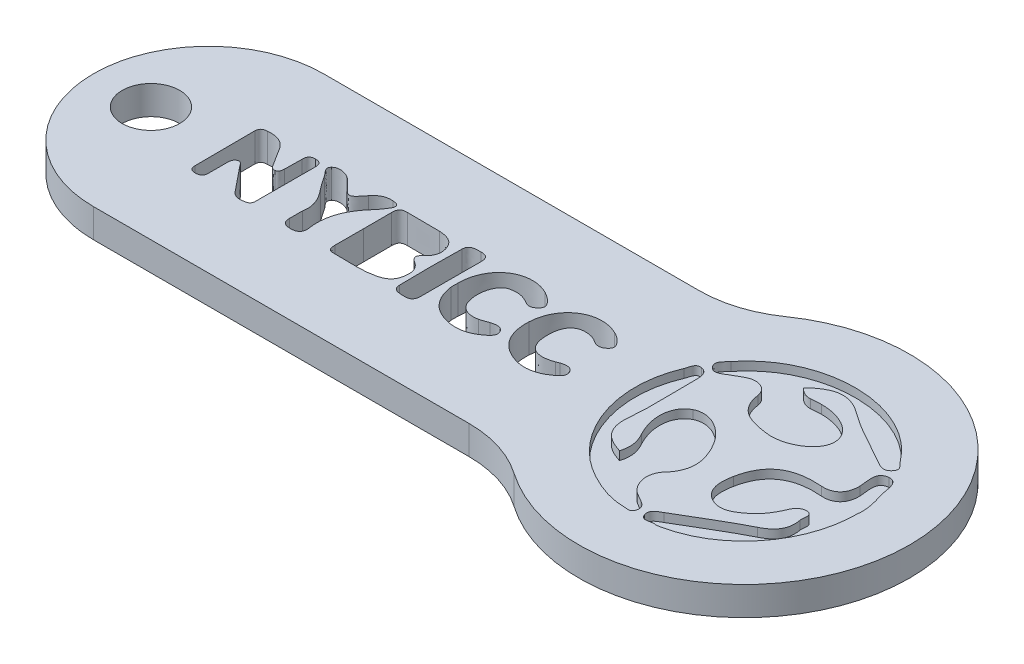
SolidWorks part; units mm, degrees
ref_plane "Plan de face" through (0, 0, 0) normal (0, 0, 1) x (1, 0, 0)
ref_plane "Plan de dessus" through (0, 0, 0) normal (0, 1, 0) x (1, 0, 0)
ref_plane "Plan de droite" through (0, 0, 0) normal (1, 0, 0) x (0, 0, -1)
sketch "Esquisse1" plane through (0, 0, 0) normal (0, 1, 0) x (1, 0, 0)
  line L0 (-14.5, 0) -> (0, 0) construction
  line L1 (-18.5, 8) -> (18.5, 8)
  line L2 (-18.5, 8) -> (-18.5, -8)
  line L3 (-18.5, -8) -> (18.5, -8)
  line L5 (-18.5, 8) -> (18.5, -8) construction
  line L6 (-18.5, -8) -> (18.5, 8) construction
  arc A0 (18.5, -8) -> (18.5, 8) centre (26.7614, 0) ccw
  circle A1 centre (-14.5, 0) radius 2
  point P0 (0, 0)
  dimension "D3" = 23
  dimension "D5" = 4
  dimension "D1" = 37
  dimension "D2" = 16
  dimension "D4" = 4
extrude "Boss.-Extru.1" add sketch "Esquisse1" along normal blind 2
sketch "Esquisse2" plane through (0, 2, 0) normal (0, 1, 0) x (1, 0, 0)
  line L0 (20.6551, -5.913) -> (-11.0872, -5.913)
  line L1 (-11.0872, -5.913) -> (-11.0872, 5.913)
  line L2 (-11.0872, 5.913) -> (20.6551, 5.913)
  line L3 (20.6551, 5.913) -> (20.5787, 5.7726)
  line L7 (18.5, 8) -> (-18.5, 8)
  line L8 (-18.5, 8) -> (-18.5, -8)
  line L9 (-18.5, -8) -> (18.5, -8)
  line L10 (18.5, 8) -> (-18.5, 8)
  line L11 (-18.5, 8) -> (-18.5, -8)
  line L12 (-18.5, -8) -> (18.5, -8)
  arc A2 (20.6551, -5.913) -> (20.6551, 5.913) centre (26.7614, 0) ccw
  arc A3 (20.6551, -5.913) -> (20.6551, 5.913) centre (26.7614, 0) ccw
  arc A4 (18.5, -8) -> (18.5, 8) centre (26.7614, 0) ccw
  arc A5 (18.5, -8) -> (18.5, 8) centre (26.7614, 0) ccw
  spline S0 degree 3 poles (0.225, -1.9246) (0.2286, -1.2609) (0.2275, -0.5975) (0.2283, 0.0661) knots 10 10 10 10 11 11 11 11
  spline S1 degree 3 poles (0.6284, -2.4527) (0.2813, -2.4644) (0.2234, -2.2089) (0.225, -1.9246) knots 9 9 9 9 10 10 10 10
  spline S2 degree 3 poles (3.5067, -2.3468) (2.5542, -2.5708) (1.5879, -2.4206) (0.6284, -2.4527) knots 8 8 8 8 9 9 9 9
  spline S3 degree 3 poles (4.4683, -1.5249) (4.3523, -2.028) (3.9703, -2.238) (3.5067, -2.3468) knots 7 7 7 7 8 8 8 8
  spline S4 degree 3 poles (4.0132, -0.175) (4.5319, -0.4973) (4.5922, -0.9877) (4.4683, -1.5249) knots 6 6 6 6 7 7 7 7
  spline S5 degree 3 poles (3.9341, 0.5259) (3.6149, 0.2483) (3.6818, 0.0309) (4.0132, -0.175) knots 5 5 5 5 6 6 6 6
  spline S6 degree 3 poles (4.2394, 1.8576) (4.4545, 1.3474) (4.3569, 0.8935) (3.9341, 0.5259) knots 4 4 4 4 5 5 5 5
  spline S7 degree 3 poles (3.0323, 2.5476) (3.5345, 2.5261) (4.0161, 2.3873) (4.2394, 1.8576) knots 3 3 3 3 4 4 4 4
  spline S8 degree 3 poles (0.7853, 2.5646) (1.5338, 2.5425) (2.2844, 2.5795) (3.0323, 2.5476) knots 2 2 2 2 3 3 3 3
  spline S9 degree 3 poles (0.2259, 1.9923) (0.215, 2.3984) (0.3606, 2.5772) (0.7853, 2.5646) knots 1 1 1 1 2 2 2 2
  spline S10 degree 3 poles (0.2283, 0.0661) (0.2291, 0.7082) (0.243, 1.3507) (0.2259, 1.9923) knots 0 0 0 0 1 1 1 1
  spline S11 degree 3 poles (-5.1722, 2.1197) (-5.1775, 1.4133) (-5.1754, 0.7068) (-5.176, 0.0003) knots 18 18 18 18 19 19 19 19
  spline S12 degree 3 poles (-5.6399, 2.5867) (-5.3196, 2.5835) (-5.1698, 2.4412) (-5.1722, 2.1197) knots 17 17 17 17 18 18 18 18
  spline S13 degree 3 poles (-6.0939, 2.115) (-6.0989, 2.4345) (-5.9709, 2.5902) (-5.6399, 2.5867) knots 16 16 16 16 17 17 17 17
  spline S14 degree 3 poles (-6.114, 0.896) (-6.0883, 1.3013) (-6.0877, 1.7087) (-6.0939, 2.115) knots 15 15 15 15 16 16 16 16
  spline S15 degree 3 poles (-6.3567, 0.4874) (-6.1454, 0.5282) (-6.1242, 0.7367) (-6.114, 0.896) knots 14 14 14 14 15 15 15 15
  spline S16 degree 3 poles (-6.7563, 0.7516) (-6.663, 0.6061) (-6.5561, 0.4488) (-6.3567, 0.4874) knots 13 13 13 13 14 14 14 14
  spline S17 degree 3 poles (-7.4724, 1.8877) (-7.2442, 1.5028) (-6.998, 1.1285) (-6.7563, 0.7516) knots 12 12 12 12 13 13 13 13
  spline S18 degree 3 poles (-8.9993, 2.5914) (-8.3468, 2.6534) (-7.8223, 2.4779) (-7.4724, 1.8877) knots 11 11 11 11 12 12 12 12
  spline S19 degree 3 poles (-9.4508, 2.1725) (-9.4369, 2.4583) (-9.2899, 2.5782) (-8.9993, 2.5914) knots 10 10 10 10 11 11 11 11
  spline S20 degree 3 poles (-9.4291, -2.0014) (-9.4372, -0.6101) (-9.4441, 0.7812) (-9.4508, 2.1725) knots 9 9 9 9 10 10 10 10
  spline S21 degree 3 poles (-9.0021, -2.437) (-9.2963, -2.4301) (-9.4357, -2.2901) (-9.4291, -2.0014) knots 8 8 8 8 9 9 9 9
  spline S22 degree 3 poles (-8.5069, -2.0014) (-8.512, -2.3343) (-8.6938, -2.4441) (-9.0021, -2.437) knots 7 7 7 7 8 8 8 8
  spline S23 degree 3 poles (-8.5036, -0.717) (-8.5043, -1.1452) (-8.5101, -1.5733) (-8.5069, -2.0014) knots 6 6 6 6 7 7 7 7
  spline S24 degree 3 poles (-8.2858, -0.219) (-8.4821, -0.3042) (-8.5032, -0.5178) (-8.5036, -0.717) knots 5 5 5 5 6 6 6 6
  spline S25 degree 3 poles (-7.8369, -0.4857) (-7.953, -0.3438) (-8.0529, -0.1181) (-8.2858, -0.219) knots 4 4 4 4 5 5 5 5
  spline S26 degree 3 poles (-6.4635, -2.1807) (-6.9172, -1.6123) (-7.376, -1.0481) (-7.8369, -0.4857) knots 3 3 3 3 4 4 4 4
  spline S27 degree 3 poles (-5.4688, -2.4272) (-5.8242, -2.5108) (-6.1923, -2.5206) (-6.4635, -2.1807) knots 2 2 2 2 3 3 3 3
  spline S28 degree 3 poles (-5.1794, -1.7337) (-5.182, -2.003) (-5.1008, -2.3406) (-5.4688, -2.4272) knots 1 1 1 1 2 2 2 2
  spline S29 degree 3 poles (-5.176, 0.0003) (-5.1766, -0.5777) (-5.174, -1.1557) (-5.1794, -1.7337) knots 0 0 0 0 1 1 1 1
  spline S30 degree 3 poles (14.6022, 1.5071) (13.5928, 1.7408) (13.0414, 1.2329) (13.0294, 0.0773) knots 11 11 11 11 12 12 12 12
  spline S31 degree 3 poles (15.1149, 1.2613) (14.9529, 1.3592) (14.7827, 1.4653) (14.6022, 1.5071) knots 10 10 10 10 11 11 11 11
  spline S32 degree 3 poles (15.9779, 1.4079) (15.76, 1.1539) (15.4505, 1.0583) (15.1149, 1.2613) knots 9 9 9 9 10 10 10 10
  spline S33 degree 3 poles (15.7902, 2.127) (15.9828, 1.9215) (16.214, 1.683) (15.9779, 1.4079) knots 8 8 8 8 9 9 9 9
  spline S34 degree 3 poles (15.1624, 2.5592) (15.3993, 2.452) (15.6134, 2.3158) (15.7902, 2.127) knots 7 7 7 7 8 8 8 8
  spline S35 degree 3 poles (11.588, 0.203) (11.6856, 2.2051) (13.4456, 3.3361) (15.1624, 2.5592) knots 6 6 6 6 7 7 7 7
  spline S36 degree 3 poles (12.9311, -2.3704) (11.8989, -1.8387) (11.5353, -0.8789) (11.588, 0.203) knots 5 5 5 5 6 6 6 6
  spline S37 degree 3 poles (15.6465, -2.1778) (14.7863, -2.8026) (13.8563, -2.8469) (12.9311, -2.3704) knots 4 4 4 4 5 5 5 5
  spline S38 degree 3 poles (16.0103, -1.3913) (16.2116, -1.7555) (15.9033, -1.9912) (15.6465, -2.1778) knots 3 3 3 3 4 4 4 4
  spline S39 degree 3 poles (15.1543, -1.1929) (15.4802, -1.0869) (15.8296, -1.0644) (16.0103, -1.3913) knots 2 2 2 2 3 3 3 3
  spline S40 degree 3 poles (14.9188, -1.2919) (14.9993, -1.2645) (15.0736, -1.2191) (15.1543, -1.1929) knots 1 1 1 1 2 2 2 2
  spline S41 degree 3 poles (13.0294, 0.0773) (13.0157, -1.2291) (13.6832, -1.7132) (14.9188, -1.2919) knots 0 0 0 0 1 1 1 1
  spline S42 degree 3 poles (6.7883, -0.4372) (6.7642, -0.2695) (6.7853, -0.0953) (6.7855, 0.0759) knots 13 13 13 13 14 14 14 14
  spline S43 degree 3 poles (8.2655, -2.4564) (7.3765, -2.0939) (6.9224, -1.3698) (6.7883, -0.4372) knots 12 12 12 12 13 13 13 13
  spline S44 degree 3 poles (10.8143, -2.1643) (10.0263, -2.763) (9.1527, -2.8182) (8.2655, -2.4564) knots 11 11 11 11 12 12 12 12
  spline S45 degree 3 poles (11.1531, -1.3675) (11.3657, -1.7257) (11.0713, -1.969) (10.8143, -2.1643) knots 10 10 10 10 11 11 11 11
  spline S46 degree 3 poles (10.2831, -1.1939) (10.6037, -1.0968) (10.9594, -1.0413) (11.1531, -1.3675) knots 9 9 9 9 10 10 10 10
  spline S47 degree 3 poles (9.6778, -1.3958) (9.8846, -1.3539) (10.0795, -1.2556) (10.2831, -1.1939) knots 8 8 8 8 9 9 9 9
  spline S48 degree 3 poles (8.2731, -0.709) (8.4644, -1.2666) (8.9952, -1.5338) (9.6778, -1.3958) knots 7 7 7 7 8 8 8 8
  spline S49 degree 3 poles (8.7857, 1.4455) (8.2295, 1.1729) (7.9857, 0.1288) (8.2731, -0.709) knots 6 6 6 6 7 7 7 7
  spline S50 degree 3 poles (9.155, 1.5328) (9.0302, 1.5112) (8.8966, 1.4998) (8.7857, 1.4455) knots 5 5 5 5 6 6 6 6
  spline S51 degree 3 poles (10.3714, 1.2365) (9.9944, 1.4594) (9.6027, 1.6104) (9.155, 1.5328) knots 4 4 4 4 5 5 5 5
  spline S52 degree 3 poles (11.1159, 1.4051) (10.9208, 1.1953) (10.6661, 1.0622) (10.3714, 1.2365) knots 3 3 3 3 4 4 4 4
  spline S53 degree 3 poles (10.9947, 2.0797) (11.1716, 1.8988) (11.3491, 1.6561) (11.1159, 1.4051) knots 2 2 2 2 3 3 3 3
  spline S54 degree 3 poles (10.3813, 2.5334) (10.6062, 2.4205) (10.8187, 2.2596) (10.9947, 2.0797) knots 1 1 1 1 2 2 2 2
  spline S55 degree 3 poles (6.7855, 0.0759) (6.7712, 2.1623) (8.6141, 3.4209) (10.3813, 2.5334) knots 0 0 0 0 1 1 1 1
  spline S56 degree 3 poles (20.8247, -2.0529) (20.69, -3.4272) (21.2917, -4.0532) (22.4958, -4.411) knots 13 13 13 13 14 14 14 14
  spline S57 degree 3 poles (20.8707, 2.5877) (20.8518, 1.04) (20.975, -0.5195) (20.8247, -2.0529) knots 12 12 12 12 13 13 13 13
  spline S58 degree 3 poles (20.3589, 3.4373) (20.7757, 3.356) (20.8759, 3.0031) (20.8707, 2.5877) knots 11 11 11 11 12 12 12 12
  spline S59 degree 3 poles (19.7877, 2.7925) (19.904, 3.0638) (19.9018, 3.5264) (20.3589, 3.4373) knots 10 10 10 10 11 11 11 11
  spline S60 degree 3 poles (23.1867, -6.7698) (19.8096, -4.9332) (18.3001, -0.6793) (19.7877, 2.7925) knots 9 9 9 9 10 10 10 10
  spline S61 degree 3 poles (25.9567, -7.6289) (24.9549, -7.6033) (24.0484, -7.2383) (23.1867, -6.7698) knots 8 8 8 8 9 9 9 9
  spline S62 degree 3 poles (26.6612, -7.3752) (26.5599, -7.7864) (26.214, -7.6353) (25.9567, -7.6289) knots 7 7 7 7 8 8 8 8
  spline S63 degree 3 poles (26.268, -6.6952) (26.5299, -6.8467) (26.7435, -7.0408) (26.6612, -7.3752) knots 6 6 6 6 7 7 7 7
  spline S64 degree 3 poles (25.7401, -6.3888) (25.9117, -6.4978) (26.0918, -6.5935) (26.268, -6.6952) knots 5 5 5 5 6 6 6 6
  spline S65 degree 3 poles (25.3508, -4.1307) (24.7364, -4.8112) (24.986, -5.9092) (25.7401, -6.3888) knots 4 4 4 4 5 5 5 5
  spline S66 degree 3 poles (25.5618, -1.0872) (26.0741, -2.135) (26.252, -3.1326) (25.3508, -4.1307) knots 3 3 3 3 4 4 4 4
  spline S67 degree 3 poles (22.5765, 0.6204) (23.5077, 1.0885) (24.8768, 0.3142) (25.5618, -1.0872) knots 2 2 2 2 3 3 3 3
  spline S68 degree 3 poles (22.2705, -2.6617) (21.4852, -1.2334) (21.6533, 0.1562) (22.5765, 0.6204) knots 1 1 1 1 2 2 2 2
  spline S69 degree 3 poles (22.4958, -4.411) (22.6895, -3.7654) (22.5874, -3.2375) (22.2705, -2.6617) knots 0 0 0 0 1 1 1 1
  spline S70 degree 3 poles (34.2908, 1.9196) (34.5116, 1.2692) (34.6572, 0.5833) (34.5723, 0.043) knots 15 15 15 15 16 16 16 16
  spline S71 degree 3 poles (33.4768, 3.345) (34.1825, 3.4033) (34.1107, 2.4507) (34.2908, 1.9196) knots 14 14 14 14 15 15 15 15
  spline S72 degree 3 poles (32.9899, 1.8117) (32.9782, 2.3605) (32.6504, 3.2769) (33.4768, 3.345) knots 13 13 13 13 14 14 14 14
  spline S73 degree 3 poles (31.6503, 0.4778) (32.418, 0.4191) (33.0107, 0.8361) (32.9899, 1.8117) knots 12 12 12 12 13 13 13 13
  spline S74 degree 3 poles (28.0087, -2.0014) (28.3864, -0.1074) (29.5871, 0.6354) (31.6503, 0.4778) knots 11 11 11 11 12 12 12 12
  spline S75 degree 3 poles (28.7232, -4.1459) (27.8705, -3.6814) (27.8418, -2.8385) (28.0087, -2.0014) knots 10 10 10 10 11 11 11 11
  spline S76 degree 3 poles (30.8285, -3.6402) (30.2151, -4.1482) (29.5238, -4.582) (28.7232, -4.1459) knots 9 9 9 9 10 10 10 10
  spline S77 degree 3 poles (31.9149, -2.0477) (31.6643, -2.6604) (31.3386, -3.2179) (30.8285, -3.6402) knots 8 8 8 8 9 9 9 9
  spline S78 degree 3 poles (32.6672, -1.5283) (32.3502, -1.494) (32.0434, -1.7332) (31.9149, -2.0477) knots 7 7 7 7 8 8 8 8
  spline S79 degree 3 poles (32.9603, -2.3153) (32.9084, -2.0339) (33.1548, -1.5813) (32.6672, -1.5283) knots 6 6 6 6 7 7 7 7
  spline S80 degree 3 poles (31.9014, -4.2266) (32.7588, -3.7947) (33.1312, -3.2385) (32.9603, -2.3153) knots 5 5 5 5 6 6 6 6
  spline S81 degree 3 poles (27.7784, -6.5813) (29.1518, -5.7938) (30.49, -4.9378) (31.9014, -4.2266) knots 4 4 4 4 5 5 5 5
  spline S82 degree 3 poles (27.221, -7.3854) (27.066, -6.9234) (27.4568, -6.7657) (27.7784, -6.5813) knots 3 3 3 3 4 4 4 4
  spline S83 degree 3 poles (28.1667, -7.6063) (27.8477, -7.5375) (27.3951, -7.903) (27.221, -7.3854) knots 2 2 2 2 3 3 3 3
  spline S84 degree 3 poles (28.5281, -7.569) (28.4093, -7.5932) (28.2794, -7.6307) (28.1667, -7.6063) knots 1 1 1 1 2 2 2 2
  spline S85 degree 3 poles (34.5723, 0.043) (34.5572, -3.6847) (31.9805, -6.8615) (28.5281, -7.569) knots 0 0 0 0 1 1 1 1
  spline S86 degree 3 poles (-2.9715, -1.8867) (-2.973, -1.6296) (-2.9712, -1.3724) (-2.9707, -0.9865) knots 12 12 12 12 13 13 13 13
  spline S87 degree 3 poles (-2.3827, -2.4792) (-2.7888, -2.4647) (-2.9692, -2.2761) (-2.9715, -1.8867) knots 11 11 11 11 12 12 12 12
  spline S88 degree 3 poles (-1.7083, -1.7964) (-1.6343, -2.2893) (-1.886, -2.4971) (-2.3827, -2.4792) knots 10 10 10 10 11 11 11 11
  spline S89 degree 3 poles (-0.5499, 1.5886) (-1.4324, 0.6279) (-1.9089, -0.4619) (-1.7083, -1.7964) knots 9 9 9 9 10 10 10 10
  spline S90 degree 3 poles (-0.1364, 2.159) (-0.265, 1.9625) (-0.392, 1.7605) (-0.5499, 1.5886) knots 8 8 8 8 9 9 9 9
  spline S91 degree 3 poles (-0.4448, 2.7623) (0.0585, 2.7305) (0.1083, 2.5327) (-0.1364, 2.159) knots 7 7 7 7 8 8 8 8
  spline S92 degree 3 poles (-1.5894, 2.2197) (-1.281, 2.6095) (-0.9475, 2.7942) (-0.4448, 2.7623) knots 6 6 6 6 7 7 7 7
  spline S93 degree 3 poles (-2.9946, 2.1544) (-2.2746, 1.3894) (-2.2599, 1.3721) (-1.5894, 2.2197) knots 5 5 5 5 6 6 6 6
  spline S94 degree 3 poles (-3.569, 2.6592) (-3.3482, 2.549) (-3.1695, 2.3403) (-2.9946, 2.1544) knots 4 4 4 4 5 5 5 5
  spline S95 degree 3 poles (-4.5969, 2.6437) (-4.3452, 2.899) (-3.899, 2.8238) (-3.569, 2.6592) knots 3 3 3 3 4 4 4 4
  spline S96 degree 3 poles (-4.318, 1.8864) (-4.4694, 2.1215) (-4.86, 2.3768) (-4.5969, 2.6437) knots 2 2 2 2 3 3 3 3
  spline S97 degree 3 poles (-3.6134, 0.892) (-3.8691, 1.2068) (-4.0981, 1.5451) (-4.318, 1.8864) knots 1 1 1 1 2 2 2 2
  spline S98 degree 3 poles (-2.9707, -0.9865) (-2.8232, -0.3301) (-3.1349, 0.3025) (-3.6134, 0.892) knots 0 0 0 0 1 1 1 1
  spline S99 degree 3 poles (28.4489, 6.1036) (27.188, 7.04) (26.1934, 6.8331) (25.1006, 5.7726) knots 13 13 13 13 14 14 14 14
  spline S100 degree 3 poles (32.2257, 3.8741) (30.9697, 4.6247) (29.6158, 5.2371) (28.4489, 6.1036) knots 12 12 12 12 13 13 13 13
  spline S101 degree 3 poles (33.1947, 3.8749) (32.8996, 3.5244) (32.5762, 3.6646) (32.2257, 3.8741) knots 11 11 11 11 12 12 12 12
  spline S102 degree 3 poles (32.9181, 4.6879) (33.0852, 4.4632) (33.51, 4.2491) (33.1947, 3.8749) knots 10 10 10 10 11 11 11 11
  spline S103 degree 3 poles (21.0052, 4.8289) (23.9283, 8.5635) (30.0923, 8.4884) (32.9181, 4.6879) knots 9 9 9 9 10 10 10 10
  spline S104 degree 3 poles (20.6512, 3.9116) (20.3706, 4.3111) (20.8091, 4.5784) (21.0052, 4.8289) knots 8 8 8 8 9 9 9 9
  spline S105 degree 3 poles (21.7112, 3.951) (21.3602, 3.7373) (20.9758, 3.4496) (20.6512, 3.9116) knots 7 7 7 7 8 8 8 8
  spline S106 degree 3 poles (22.4531, 4.3729) (22.1989, 4.2458) (21.9541, 4.099) (21.7112, 3.951) knots 6 6 6 6 7 7 7 7
  spline S107 degree 3 poles (23.9755, 3.7431) (23.8907, 4.348) (23.204, 4.7486) (22.4531, 4.3729) knots 5 5 5 5 6 6 6 6
  spline S108 degree 3 poles (26.5035, 1.7576) (25.3358, 1.9291) (24.1957, 2.1695) (23.9755, 3.7431) knots 4 4 4 4 5 5 5 5
  spline S109 degree 3 poles (29.457, 3.5205) (29.4094, 2.5046) (27.9199, 1.5498) (26.5035, 1.7576) knots 3 3 3 3 4 4 4 4
  spline S110 degree 3 poles (26.7445, 5.4024) (28.3033, 5.391) (29.5054, 4.5538) (29.457, 3.5205) knots 2 2 2 2 3 3 3 3
  spline S111 degree 3 poles (26.0136, 5.3603) (26.2569, 5.3802) (26.5009, 5.4042) (26.7445, 5.4024) knots 1 1 1 1 2 2 2 2
  spline S112 degree 3 poles (25.1006, 5.7726) (25.3972, 5.4799) (25.6664, 5.3319) (26.0136, 5.3603) knots 0 0 0 0 1 1 1 1
  spline S113 degree 3 poles (6.2957, 2.1656) (6.2889, 1.4614) (6.2923, 0.7571) (6.2917, 0.0529) knots 6 6 6 6 7 7 7 7
  spline S114 degree 3 poles (5.7113, 2.7436) (6.1126, 2.754) (6.2995, 2.5672) (6.2957, 2.1656) knots 5 5 5 5 6 6 6 6
  spline S115 degree 3 poles (4.8778, 2.2684) (4.8908, 2.7581) (5.3424, 2.734) (5.7113, 2.7436) knots 4 4 4 4 5 5 5 5
  spline S116 degree 3 poles (4.8746, -2.0826) (4.8408, -0.6328) (4.8396, 0.8188) (4.8778, 2.2684) knots 3 3 3 3 4 4 4 4
  spline S117 degree 3 poles (5.7365, -2.5991) (5.3325, -2.5938) (4.8868, -2.606) (4.8746, -2.0826) knots 2 2 2 2 3 3 3 3
  spline S118 degree 3 poles (6.2899, -1.9959) (6.2905, -2.369) (6.1719, -2.6048) (5.7365, -2.5991) knots 1 1 1 1 2 2 2 2
  spline S119 degree 3 poles (6.2917, 0.0529) (6.2911, -0.63) (6.2888, -1.313) (6.2899, -1.9959) knots 0 0 0 0 1 1 1 1
  dimension "D1" = 3
  dimension "D2" = 0
sketch "Esquisse3" plane through (0, 2, 0) normal (0, 1, 0) x (1, 0, 0)
  line L0 (-18.5, -8) -> (18.5, -8) construction
  line L1 (18.5, 8) -> (-18.5, 8) construction
  line L2 (-18.5, 8) -> (-18.5, -8) construction
  line L3 (-18.5, -8) -> (18.5, -8)
  line L4 (18.5, 8) -> (-18.5, 8)
  line L5 (-18.5, 8) -> (-18.5, -8)
  line L6 (20.6551, -5.913) -> (-11.0872, -5.913) construction
  line L7 (-11.0872, -5.913) -> (-11.0872, 5.913) construction
  line L8 (-11.0872, 5.913) -> (20.6551, 5.913) construction
  line L9 (20.6551, -5.913) -> (-11.0872, -5.913)
  line L10 (-11.0872, -5.913) -> (-11.0872, 5.913)
  line L11 (-11.0872, 5.913) -> (20.6551, 5.913)
  arc A0 (18.5, -8) -> (18.5, 8) centre (26.7614, 0) ccw construction
  arc A1 (18.5, -8) -> (18.5, 8) centre (26.7614, 0) ccw
  arc A2 (20.6551, -5.913) -> (20.6551, 5.913) centre (26.7614, 0) ccw construction
  arc A3 (20.6551, -5.913) -> (20.6551, 5.913) centre (26.7614, 0) ccw
  circle A4 centre (-14.5, 0) radius 2 construction
  circle A5 centre (-14.5, 0) radius 2
sketch "Esquisse4" plane through (0, 2, 0) normal (0, 1, 0) x (1, 0, 0)
  line L0 (20.6551, 5.913) -> (20.5787, 5.7726) construction
  line L7 (20.6551, 5.913) -> (20.5787, 5.7726)
  spline S0 degree 3 poles (-2982.0321, -306.2248) (2982.2581, 103.2699) (-2981.6444, -105.1439) (2982.0145, 307.7935) knots -65.695393 -65.695393 -65.695393 -65.695393 87.11992 87.11992 87.11992 87.11992 only from (0.225, -1.9246) to (0.2283, 0.0661) construction
  spline S1 degree 3 poles (2999.5682, 0.4278) (-2999.8564, -103.9529) (3000.3037, 105.1379) (-2999.0596, 1.1227) knots -40.537107 -40.537107 -40.537107 -40.537107 41.130987 41.130987 41.130987 41.130987 only from (0.2283, 0.0661) to (0.2259, 1.9923) construction
  spline S2 degree 3 poles (-2594.1466, -1484.3682) (2742.4634, 1004.8177) (-2871.3247, -600.9655) (2983.9031, 280.5652) knots -27.989827 -27.989827 -27.989827 -27.989827 28.752727 28.752727 28.752727 28.752727 only from (0.2259, 1.9923) to (0.7853, 2.5646) construction
  spline S3 degree 3 poles (51.5824, 3001.694) (-133.9703, -2997.156) (137.8597, 3002.2619) (-48.6688, -2996.538) knots -26.157281 -26.157281 -26.157281 -26.157281 31.080499 31.080499 31.080499 31.080499 only from (0.7853, 2.5646) to (3.0323, 2.5476) construction
  spline S4 degree 3 poles (2009.6493, 2232.5005) (-2006.0549, -2261.7938) (1972.7573, 2299.3914) (-1888.9186, -2324.9431) knots -17.557346 -17.557346 -17.557346 -17.557346 22.989169 22.989169 22.989169 22.989169 only from (3.0323, 2.5476) to (4.2394, 1.8576) construction
  spline S5 degree 3 poles (-825.3245, -2787.801) (-643.4265, 2631.1826) (1608.761, -2358.0246) (-2178.4925, 2039.7568) knots -43.629744 -43.629744 -43.629744 -43.629744 43.39188 43.39188 43.39188 43.39188 only from (4.2394, 1.8576) to (3.9341, 0.5259) construction
  spline S6 degree 3 poles (2844.7759, 963.7921) (-2876.8731, -1060.506) (2838.2734, 1189.6036) (-2665.5674, -1363.5437) knots -20.650114 -20.650114 -20.650114 -20.650114 36.446421 36.446421 36.446421 36.446421 only from (3.9341, 0.5259) to (4.0132, -0.175) construction
  spline S7 degree 3 poles (-2766.0668, -1151.1511) (2784.3818, 1220.8463) (-2765.0092, -1253.3988) (2740.6322, 1228.3167) knots -13.985195 -13.985195 -13.985195 -13.985195 29.240127 29.240127 29.240127 29.240127 only from (4.0132, -0.175) to (4.4683, -1.5249) construction
  spline S8 degree 3 poles (-2041.5863, 2192.2627) (2100.3276, -2184.7351) (-2103.0074, 2172.4151) (2071.9559, -2174.9533) knots -13.982728 -13.982728 -13.982728 -13.982728 30.958336 30.958336 30.958336 30.958336 only from (4.4683, -1.5249) to (3.5067, -2.3468) construction
  spline S9 degree 3 poles (-59.3201, 2996.7539) (129.9649, -3003.5516) (-126.8548, 2998.569) (62.5749, -3001.4884) knots -8.86397 -8.86397 -8.86397 -8.86397 26.208592 26.208592 26.208592 26.208592 only from (3.5067, -2.3468) to (0.6284, -2.4527) construction
  spline S10 degree 3 poles (2111.4901, 2129.1121) (-2098.1565, -2170.5449) (2084.4213, 2180.9807) (-2068.4391, -2174.5205) knots -10.690662 -10.690662 -10.690662 -10.690662 31.066809 31.066809 31.066809 31.066809 only from (0.6284, -2.4527) to (0.225, -1.9246) construction
  spline S11 degree 3 poles (-348.132, -2949.361) (1153.6825, 2295.7904) (-1977.1505, -1448.0147) (2927.5221, 384.2302) knots -14.264316 -14.264316 -14.264316 -14.264316 39.479423 39.479423 39.479423 39.479423 only from (14.6022, 1.5071) to (13.0294, 0.0773) construction
  spline S12 degree 3 poles (2948.4033, 347.3048) (-2187.816, 787.9674) (1421.8733, -1874.4898) (-543.1272, 2902.7051) knots -24.639929 -24.639929 -24.639929 -24.639929 25.558939 25.558939 25.558939 25.558939 only from (13.0294, 0.0773) to (14.9188, -1.2919) construction
  spline S13 degree 3 poles (-958.1483, 2836.3928) (974.8222, -2845.1141) (-944.5177, 2842.7267) (987.4974, -2839.1796) knots -40.965757 -40.965757 -40.965757 -40.965757 43.934538 43.934538 43.934538 43.934538 only from (14.9188, -1.2919) to (15.1543, -1.1929) construction
  spline S14 degree 3 poles (1834.0952, 2384.2611) (-1781.7103, -2431.8551) (1763.0904, 2463.8486) (-1658.2791, -2490.2535) knots -19.116516 -19.116516 -19.116516 -19.116516 22.783936 22.783936 22.783936 22.783936 only from (15.1543, -1.1929) to (16.0103, -1.3913) construction
  spline S15 degree 3 poles (-2944.9557, 480.1005) (2999.5577, -437.1195) (-2973.0865, 399.1902) (2991.1962, -383.3809) knots -13.526295 -13.526295 -13.526295 -13.526295 21.371458 21.371458 21.371458 21.371458 only from (16.0103, -1.3913) to (15.6465, -2.1778) construction
  spline S16 degree 3 poles (-1566.3264, 2534.7247) (2051.528, -2222.9537) (-2481.2826, 1586.895) (2909.5968, -512.0463) knots -23.179984 -23.179984 -23.179984 -23.179984 39.168029 39.168029 39.168029 39.168029 only from (15.6465, -2.1778) to (12.9311, -2.3704) construction
  spline S17 degree 3 poles (2137.7771, 2113.1028) (-2015.8157, -2312.7506) (1896.5246, 2442.5114) (-1679.2144, -2476.4052) knots -12.834342 -12.834342 -12.834342 -12.834342 26.665789 26.665789 26.665789 26.665789 only from (12.9311, -2.3704) to (11.588, 0.203) construction
  spline S18 degree 3 poles (2839.5821, 979.7641) (-2656.3811, -1375.7454) (2464.1202, 1739.6498) (-2161.0995, -2052.3909) knots -4.94192 -4.94192 -4.94192 -4.94192 17.913939 17.913939 17.913939 17.913939 only from (11.588, 0.203) to (15.1624, 2.5592) construction
  spline S19 degree 3 poles (1510.985, 2602.6074) (-1552.1611, -2572.6268) (1598.0144, 2567.9488) (-1535.4163, -2565.4835) knots -41.995983 -41.995983 -41.995983 -41.995983 53.363625 53.363625 53.363625 53.363625 only from (15.1624, 2.5592) to (15.7902, 2.127) construction
  spline S20 degree 3 poles (3015.6348, 2.4047) (-2997.8609, -4.8648) (3029.2533, 30.8991) (-2983.1374, -63.8689) knots -10.045119 -10.045119 -10.045119 -10.045119 26.196193 26.196193 26.196193 26.196193 only from (15.7902, 2.127) to (15.9779, 1.4079) construction
  spline S21 degree 3 poles (-1549.1347, -2555.3428) (1391.783, 2695.2672) (-1162.449, -2783.2851) (991.3263, 2836.1786) knots -18.58527 -18.58527 -18.58527 -18.58527 35.231852 35.231852 35.231852 35.231852 only from (15.9779, 1.4079) to (15.1149, 1.2613) construction
  spline S22 degree 3 poles (95.5079, 3000.0856) (-62.8496, -3010.3393) (113.121, 3012.0828) (-125.8263, -2994.9698) knots -24.511096 -24.511096 -24.511096 -24.511096 44.727739 44.727739 44.727739 44.727739 only from (15.1149, 1.2613) to (14.6022, 1.5071) construction
  spline S23 degree 3 poles (2991.3697, 111.9861) (-3001.8516, 37.0039) (2991.5458, -37.9783) (-3001.8604, -112.9605) knots -64.579708 -64.579708 -64.579708 -64.579708 65.141973 65.141973 65.141973 65.141973 only from (-5.176, 0.0003) to (-5.1794, -1.7337) construction
  spline S24 degree 3 poles (2989.89, 135.626) (-3000.2375, 54.0237) (2989.8547, -53.0066) (-3000.1489, -134.048) knots -47.926681 -47.926681 -47.926681 -47.926681 85.380927 85.380927 85.380927 85.380927 only from (-5.1722, 2.1197) to (-5.176, 0.0003) construction
  spline S25 degree 3 poles (-2153.2815, 2064.2448) (1424.0711, -2402.4044) (-836.3022, 2709.862) (331.7858, -2969.2518) knots -23.860655 -23.860655 -23.860655 -23.860655 55.723257 55.723257 55.723257 55.723257 only from (-5.6399, 2.5867) to (-5.1722, 2.1197) construction
  spline S26 degree 3 poles (-2850.7548, -910.9558) (2919.3178, 374.5288) (-2974.0352, 38.0522) (2972.4393, -333.115) knots -20.378659 -20.378659 -20.378659 -20.378659 49.105246 49.105246 49.105246 49.105246 only from (-6.0939, 2.115) to (-5.6399, 2.5867) construction
  spline S27 degree 3 poles (-2970.5078, 457.8634) (2958.2056, -555.3162) (-2968.3508, 574.2394) (2952.1212, -494.1318) knots -38.421322 -38.421322 -38.421322 -38.421322 71.156716 71.156716 71.156716 71.156716 only from (-6.114, 0.896) to (-6.0939, 2.115) construction
  spline S28 degree 3 poles (-1965.1544, 2272.4229) (1921.8618, -2310.2499) (-1904.3367, 2336.6874) (1863.6352, -2344.9971) knots -7.139946 -7.139946 -7.139946 -7.139946 36.92124 36.92124 36.92124 36.92124 only from (-6.3567, 0.4874) to (-6.114, 0.896) construction
  spline S29 degree 3 poles (-1054.9441, -2810.0063) (1050.367, 2818.4842) (-1081.7562, -2810.0805) (1095.1224, 2790.7133) knots -10.807958 -10.807958 -10.807958 -10.807958 36.862166 36.862166 36.862166 36.862166 only from (-6.7563, 0.7516) to (-6.3567, 0.4874) construction
  spline S30 degree 3 poles (2543.5555, 1579.5535) (-2604.8686, -1503.9322) (2591.2874, 1505.5793) (-2558.0032, -1576.7089) knots -35.938353 -35.938353 -35.938353 -35.938353 61.545934 61.545934 61.545934 61.545934 only from (-7.4724, 1.8877) to (-6.7563, 0.7516) construction
  spline S31 degree 3 poles (567.7958, 2945.1059) (-767.2962, -2960.8783) (822.8027, 2943.5513) (-833.8392, -2882.0037) knots -15.937915 -15.937915 -15.937915 -15.937915 35.0837 35.0837 35.0837 35.0837 only from (-8.9993, 2.5914) to (-7.4724, 1.8877) construction
  spline S32 degree 3 poles (28.4644, -2993.879) (277.6471, 2932.9339) (-709.155, -2839.7103) (1208.0554, 2732.3375) knots -24.232003 -24.232003 -24.232003 -24.232003 48.696631 48.696631 48.696631 48.696631 only from (-9.4508, 2.1725) to (-8.9993, 2.5914) construction
  spline S33 degree 3 poles (2857.7069, -776.2907) (-2871.2407, 20.2347) (2850.6659, -17.9582) (-2871.6017, 789.4215) knots -127.155557 -127.155557 -127.155557 -127.155557 147.31009 147.31009 147.31009 147.31009 only from (-9.4291, -2.0014) to (-9.4508, 2.1725) construction
  spline S34 degree 3 poles (2693.2721, -1196.6217) (-1648.8695, 1860.0323) (735.4754, -2458.2345) (-6.8346, 2977.8397) knots -45.248039 -45.248039 -45.248039 -45.248039 58.347774 58.347774 58.347774 58.347774 only from (-9.0021, -2.437) to (-9.4291, -2.0014) construction
  spline S35 degree 3 poles (-1406.3726, 2652.1823) (1348.518, -2718.4862) (-1267.9012, 2761.4218) (1077.8974, -2797.2123) knots -20.18475 -20.18475 -20.18475 -20.18475 38.895479 38.895479 38.895479 38.895479 only from (-8.5069, -2.0014) to (-9.0021, -2.437) construction
  spline S36 degree 3 poles (-3006.376, 94.5843) (2989.9983, 5.7059) (-3007.0337, -8.4595) (2989.4363, -95.7513) knots -53.348757 -53.348757 -53.348757 -53.348757 66.067261 66.067261 66.067261 66.067261 only from (-8.5036, -0.717) to (-8.5069, -2.0014) construction
  spline S37 degree 3 poles (2229.893, -1997.5388) (-2227.3921, 2036.8085) (2190.8139, -2059.7449) (-2188.1871, 2060.4819) knots -18.254974 -18.254974 -18.254974 -18.254974 30.309368 30.309368 30.309368 30.309368 only from (-8.2858, -0.219) to (-8.5036, -0.717) construction
  spline S38 degree 3 poles (1012.8533, 2820.4962) (-1028.9415, -2830.0317) (1022.1983, 2825.8867) (-1055.8507, -2811.2383) knots -14.827096 -14.827096 -14.827096 -14.827096 23.213079 23.213079 23.213079 23.213079 only from (-7.8369, -0.4857) to (-8.2858, -0.219) construction
  spline S39 degree 3 poles (-2264.28, -1971.6814) (2418.2632, 1764.7617) (-2437.7743, -1760.9741) (2252.1522, 1966.117) knots -87.097842 -87.097842 -87.097842 -87.097842 96.535082 96.535082 96.535082 96.535082 only from (-6.4635, -2.1807) to (-7.8369, -0.4857) construction
  spline S40 degree 3 poles (-1146.2684, -2776.9723) (1131.44, 2794.2873) (-1107.7125, -2812.167) (1033.1633, 2811.6903) knots -19.874716 -19.874716 -19.874716 -19.874716 23.440495 23.440495 23.440495 23.440495 only from (-5.4688, -2.4272) to (-6.4635, -2.1807) construction
  spline S41 degree 3 poles (2568.0048, -1543.9665) (-2583.5789, 1551.7322) (2577.7396, -1547.8337) (-2591.8951, 1517.2547) knots -15.744794 -15.744794 -15.744794 -15.744794 18.088642 18.088642 18.088642 18.088642 only from (-5.1794, -1.7337) to (-5.4688, -2.4272) construction
  spline S42 degree 3 poles (-2958.381, 423.5428) (3002.5799, -381.3482) (-2985.0311, 344.8063) (2992.5981, -330.9635) knots -6.698907 -6.698907 -6.698907 -6.698907 28.58634 28.58634 28.58634 28.58634 only from (11.1531, -1.3675) to (10.8143, -2.1643) construction
  spline S43 degree 3 poles (1554.7818, 2570.4885) (-1524.6632, -2600.5468) (1510.5046, 2617.8559) (-1430.408, -2632.0808) knots -10.76817 -10.76817 -10.76817 -10.76817 28.672218 28.672218 28.672218 28.672218 only from (10.2831, -1.1939) to (11.1531, -1.3675) construction
  spline S44 degree 3 poles (-655.9986, 2923.7516) (651.9477, -2935.6544) (-632.9831, 2932.8279) (679.4642, -2925.4989) knots -22.986962 -22.986962 -22.986962 -22.986962 40.197873 40.197873 40.197873 40.197873 only from (9.6778, -1.3958) to (10.2831, -1.1939) construction
  spline S45 degree 3 poles (2856.4587, -916.4314) (-2637.9023, 1335.4528) (2404.0422, -1745.3084) (-2083.0988, 2134.9347) knots -16.1158 -16.1158 -16.1158 -16.1158 31.351771 31.351771 31.351771 31.351771 only from (8.2731, -0.709) to (9.6778, -1.3958) construction
  spline S46 degree 3 poles (-360.8692, -2974.2022) (571.4544, 2981.2626) (-747.8209, -2937.5614) (955.1924, 2844.0583) knots -7.761652 -7.761652 -7.761652 -7.761652 21.126773 21.126773 21.126773 21.126773 only from (8.7857, 1.4455) to (8.2731, -0.709) construction
  spline S47 degree 3 poles (-1516.2115, 2584.7093) (1547.558, -2581.8978) (-1524.05, 2588.0367) (1518.2782, -2590.9675) knots -31.275404 -31.275404 -31.275404 -31.275404 41.704134 41.704134 41.704134 41.704134 only from (9.155, 1.5328) to (8.7857, 1.4455) construction
  spline S48 degree 3 poles (820.6755, 2889.4774) (-753.5804, -2916.3367) (769.4511, 2919.6859) (-781.2622, -2892.292) knots -22.942366 -22.942366 -22.942366 -22.942366 30.037319 30.037319 30.037319 30.037319 only from (10.3714, 1.2365) to (9.155, 1.5328) construction
  spline S49 degree 3 poles (-343.7483, -2977.2703) (308.1702, 3008.3894) (-212.7774, -3010.8971) (147.8081, 2997.7206) knots -20.842434 -20.842434 -20.842434 -20.842434 26.221229 26.221229 26.221229 26.221229 only from (11.1159, 1.4051) to (10.3714, 1.2365) construction
  spline S50 degree 3 poles (2977.588, -443.9598) (-2974.9457, 416.7555) (3002.6336, -367.0798) (-2972.6097, 311.4831) knots -17.340012 -17.340012 -17.340012 -17.340012 21.379784 21.379784 21.379784 21.379784 only from (10.9947, 2.0797) to (11.1159, 1.4051) construction
  spline S51 degree 3 poles (1746.6078, -2442.7306) (-1872.7626, 2381.3018) (2009.4208, -2281.8479) (-2069.6362, 2161.9686) knots -41.281471 -41.281471 -41.281471 -41.281471 44.823321 44.823321 44.823321 44.823321 only from (10.3813, 2.5334) to (10.9947, 2.0797) construction
  spline S52 degree 3 poles (2773.0057, 1143.5896) (-2584.4348, -1521.2222) (2371.2938, 1862.3972) (-2071.5977, -2148.7592) knots -10.385418 -10.385418 -10.385418 -10.385418 11.301025 11.301025 11.301025 11.301025 only from (6.7855, 0.0759) to (10.3813, 2.5334) construction
  spline S53 degree 3 poles (2979.5687, 402.4884) (-2966.9556, -427.1046) (2980.4966, 426.9029) (-2965.9429, -402.5793) knots -21.855628 -21.855628 -21.855628 -21.855628 49.223658 49.223658 49.223658 49.223658 only from (6.7883, -0.4372) to (6.7855, 0.0759) construction
  spline S54 degree 3 poles (2007.7271, 2232.2382) (-1927.0081, -2443.1365) (1813.7271, 2559.8061) (-1598.3545, -2533.7182) knots -10.372644 -10.372644 -10.372644 -10.372644 40.161907 40.161907 40.161907 40.161907 only from (8.2655, -2.4564) to (6.7883, -0.4372) construction
  spline S55 degree 3 poles (-1101.4373, 2781.1181) (1421.9667, -2807.2673) (-1678.6973, 2674.0482) (1890.9524, -2330.7888) knots -13.173982 -13.173982 -13.173982 -13.173982 42.267473 42.267473 42.267473 42.267473 only from (10.8143, -2.1643) to (8.2655, -2.4564) construction
  spline S86 degree 3 poles (-2996.4431, 152.39) (2950.5158, 121.4106) (-2932.3411, -386.8471) (2923.4592, 656.5887) knots -7.467958 -7.467958 -7.467958 -7.467958 18.404267 18.404267 18.404267 18.404267 only from (-2.9946, 2.1544) to (-1.5894, 2.2197) construction
  spline S87 degree 3 poles (-952.1225, -2843.2164) (909.3004, 2874.942) (-899.1265, -2875.8655) (896.9632, 2863.952) knots -23.85707 -23.85707 -23.85707 -23.85707 33.534514 33.534514 33.534514 33.534514 only from (-3.569, 2.6592) to (-2.9946, 2.1544) construction
  spline S88 degree 3 poles (2256.6654, -1967.8313) (-2359.5281, 1897.8388) (2420.219, -1805.5158) (-2468.044, 1712.4812) knots -15.813471 -15.813471 -15.813471 -15.813471 23.628618 23.628618 23.628618 23.628618 only from (-4.5969, 2.6437) to (-3.569, 2.6592) construction
  spline S89 degree 3 poles (-3004.0454, 32.8507) (3008.071, -35.3317) (-3017.0707, 31.4195) (2995.2517, -4.4772) knots -12.724886 -12.724886 -12.724886 -12.724886 17.260861 17.260861 17.260861 17.260861 only from (-4.318, 1.8864) to (-4.5969, 2.6437) construction
  spline S90 degree 3 poles (2011.4312, 2222.7234) (-1961.8481, -2299.4702) (1935.7614, 2319.3444) (-1969.3238, -2264.7305) knots -45.814849 -45.814849 -45.814849 -45.814849 50.430663 50.430663 50.430663 50.430663 only from (-3.6134, 0.892) to (-4.318, 1.8864) construction
  spline S91 degree 3 poles (-3001.1137, 90.1637) (3040.2793, -184.52) (-3047.4979, 239.6201) (2986.5184, -240.696) knots -20.245593 -20.245593 -20.245593 -20.245593 23.375097 23.375097 23.375097 23.375097 only from (-2.9707, -0.9865) to (-3.6134, 0.892) construction
  spline S92 degree 3 poles (113.0906, -2999.5436) (-113.4922, 2966.9437) (102.1765, -2971.1857) (-102.916, 2997.1897) knots -16.484889 -16.484889 -16.484889 -16.484889 40.489407 40.489407 40.489407 40.489407 only from (-2.9715, -1.8867) to (-2.9707, -0.9865) construction
  spline S93 degree 3 poles (2942.4896, -513.9583) (-2611.4586, 1014.9878) (2229.904, -1629.7706) (-1818.6892, 2355.0464) knots -24.17823 -24.17823 -24.17823 -24.17823 49.909133 49.909133 49.909133 49.909133 only from (-2.3827, -2.4792) to (-2.9715, -1.8867) construction
  spline S94 degree 3 poles (-2353.9092, 1859.7909) (2533.9538, -1907.396) (-2609.0759, 1858.2353) (2479.0152, -1687.9979) knots -17.17505 -17.17505 -17.17505 -17.17505 45.850426 45.850426 45.850426 45.850426 only from (-1.7083, -1.7964) to (-2.3827, -2.4792) construction
  spline S95 degree 3 poles (-2695.404, 1316.1839) (2849.9552, -1197.4463) (-2854.5611, 1172.2088) (2749.0651, -1198.2088) knots -14.267337 -14.267337 -14.267337 -14.267337 29.386176 29.386176 29.386176 29.386176 only from (-0.5499, 1.5886) to (-1.7083, -1.7964) construction
  spline S96 degree 3 poles (2018.2709, -2217.1443) (-2004.3521, 2246.8967) (2010.1202, -2236.9907) (-2036.9952, 2204.1938) knots -31.53802 -31.53802 -31.53802 -31.53802 47.751392 47.751392 47.751392 47.751392 only from (-0.1364, 2.159) to (-0.5499, 1.5886) construction
  spline S97 degree 3 poles (-2995.8704, -143.8306) (3047.9622, -25.5263) (-3029.0127, 297.4495) (2913.0498, -683.4376) knots -16.931206 -16.931206 -16.931206 -16.931206 36.40834 36.40834 36.40834 36.40834 only from (-0.4448, 2.7623) to (-0.1364, 2.159) construction
  spline S98 degree 3 poles (-2984.8496, -262.2673) (2930.1448, -89.7162) (-2916.047, 395.1628) (2927.9548, -639.051) knots -21.564796 -21.564796 -21.564796 -21.564796 33.049399 33.049399 33.049399 33.049399 only from (-1.5894, 2.2197) to (-0.4448, 2.7623) construction
  spline S99 degree 3 poles (3003.2651, 94.6318) (-2990.8015, 74.6586) (3003.383, -73.5124) (-2990.6772, -92.8589) knots -52.860545 -52.860545 -52.860545 -52.860545 66.293897 66.293897 66.293897 66.293897 only from (6.2957, 2.1656) to (6.2917, 0.0529) construction
  spline S100 degree 3 poles (-2990.004, 68.166) (3002.9632, 159.2728) (-2990.3784, -160.1813) (3002.5752, -70.6201) knots -83.531233 -83.531233 -83.531233 -83.531233 84.214899 84.214899 84.214899 84.214899 only from (6.2917, 0.0529) to (6.2899, -1.9959) construction
  spline S101 degree 3 poles (2722.8431, -1273.1486) (-2682.7411, 1387.2058) (2660.8293, -1455.4313) (-2607.7549, 1470.1596) knots -23.58183 -23.58183 -23.58183 -23.58183 24.068138 24.068138 24.068138 24.068138 only from (6.2899, -1.9959) to (5.7365, -2.5991) construction
  spline S102 degree 3 poles (-1950.0465, -2277.3639) (1979.5386, 2278.5663) (-1960.2195, -2290.4862) (1937.4442, 2292.3373) knots -13.990466 -13.990466 -13.990466 -13.990466 18.100794 18.100794 18.100794 18.100794 only from (5.7365, -2.5991) to (4.8746, -2.0826) construction
  spline S103 degree 3 poles (-2610.5837, 1462.6253) (2742.907, -1728.5017) (-2798.6504, 1518.9891) (2827.5493, -976.8193) knots -73.733285 -73.733285 -73.733285 -73.733285 72.361183 72.361183 72.361183 72.361183 only from (4.8746, -2.0826) to (4.8778, 2.2684) construction
  spline S104 degree 3 poles (2044.7685, -2197.2023) (-2071.1528, 2189.4887) (2095.76, -2171.3613) (-2073.8689, 2164.7481) knots -10.959437 -10.959437 -10.959437 -10.959437 20.744442 20.744442 20.744442 20.744442 only from (4.8778, 2.2684) to (5.7113, 2.7436) construction
  spline S105 degree 3 poles (-2958.4378, 270.6131) (2318.0992, -1010.7871) (-1622.1248, 1862.6957) (919.85, -2814.6825) knots -37.156168 -37.156168 -37.156168 -37.156168 50.094159 50.094159 50.094159 50.094159 only from (5.7113, 2.7436) to (6.2957, 2.1656) construction
  spline S120 degree 3 poles (0.225, -1.9246) (0.2286, -1.2609) (0.2275, -0.5975) (0.2283, 0.0661) knots 10 10 10 10 11 11 11 11
  spline S121 degree 3 poles (0.2283, 0.0661) (0.2291, 0.7082) (0.243, 1.3507) (0.2259, 1.9923) knots 0 0 0 0 1 1 1 1
  spline S122 degree 3 poles (0.2259, 1.9923) (0.215, 2.3984) (0.3606, 2.5772) (0.7853, 2.5646) knots 1 1 1 1 2 2 2 2
  spline S123 degree 3 poles (0.7853, 2.5646) (1.5338, 2.5425) (2.2844, 2.5795) (3.0323, 2.5476) knots 2 2 2 2 3 3 3 3
  spline S124 degree 3 poles (3.0323, 2.5476) (3.5345, 2.5261) (4.0161, 2.3873) (4.2394, 1.8576) knots 3 3 3 3 4 4 4 4
  spline S125 degree 3 poles (4.2394, 1.8576) (4.4545, 1.3474) (4.3569, 0.8935) (3.9341, 0.5259) knots 4 4 4 4 5 5 5 5
  spline S126 degree 3 poles (3.9341, 0.5259) (3.6149, 0.2483) (3.6818, 0.0309) (4.0132, -0.175) knots 5 5 5 5 6 6 6 6
  spline S127 degree 3 poles (4.0132, -0.175) (4.5319, -0.4973) (4.5922, -0.9877) (4.4683, -1.5249) knots 6 6 6 6 7 7 7 7
  spline S128 degree 3 poles (4.4683, -1.5249) (4.3523, -2.028) (3.9703, -2.238) (3.5067, -2.3468) knots 7 7 7 7 8 8 8 8
  spline S129 degree 3 poles (3.5067, -2.3468) (2.5542, -2.5708) (1.5879, -2.4206) (0.6284, -2.4527) knots 8 8 8 8 9 9 9 9
  spline S130 degree 3 poles (0.6284, -2.4527) (0.2813, -2.4644) (0.2234, -2.2089) (0.225, -1.9246) knots 9 9 9 9 10 10 10 10
  spline S131 degree 3 poles (14.6022, 1.5071) (13.5928, 1.7408) (13.0414, 1.2329) (13.0294, 0.0773) knots 11 11 11 11 12 12 12 12
  spline S132 degree 3 poles (13.0294, 0.0773) (13.0157, -1.2291) (13.6832, -1.7132) (14.9188, -1.2919) knots 0 0 0 0 1 1 1 1
  spline S133 degree 3 poles (14.9188, -1.2919) (14.9993, -1.2645) (15.0736, -1.2191) (15.1543, -1.1929) knots 1 1 1 1 2 2 2 2
  spline S134 degree 3 poles (15.1543, -1.1929) (15.4802, -1.0869) (15.8296, -1.0644) (16.0103, -1.3913) knots 2 2 2 2 3 3 3 3
  spline S135 degree 3 poles (16.0103, -1.3913) (16.2116, -1.7555) (15.9033, -1.9912) (15.6465, -2.1778) knots 3 3 3 3 4 4 4 4
  spline S136 degree 3 poles (15.6465, -2.1778) (14.7863, -2.8026) (13.8563, -2.8469) (12.9311, -2.3704) knots 4 4 4 4 5 5 5 5
  spline S137 degree 3 poles (12.9311, -2.3704) (11.8989, -1.8387) (11.5353, -0.8789) (11.588, 0.203) knots 5 5 5 5 6 6 6 6
  spline S138 degree 3 poles (11.588, 0.203) (11.6856, 2.2051) (13.4456, 3.3361) (15.1624, 2.5592) knots 6 6 6 6 7 7 7 7
  spline S139 degree 3 poles (15.1624, 2.5592) (15.3993, 2.452) (15.6134, 2.3158) (15.7902, 2.127) knots 7 7 7 7 8 8 8 8
  spline S140 degree 3 poles (15.7902, 2.127) (15.9828, 1.9215) (16.214, 1.683) (15.9779, 1.4079) knots 8 8 8 8 9 9 9 9
  spline S141 degree 3 poles (15.9779, 1.4079) (15.76, 1.1539) (15.4505, 1.0583) (15.1149, 1.2613) knots 9 9 9 9 10 10 10 10
  spline S142 degree 3 poles (15.1149, 1.2613) (14.9529, 1.3592) (14.7827, 1.4653) (14.6022, 1.5071) knots 10 10 10 10 11 11 11 11
  spline S143 degree 3 poles (-5.176, 0.0003) (-5.1766, -0.5777) (-5.174, -1.1557) (-5.1794, -1.7337) knots 0 0 0 0 1 1 1 1
  spline S144 degree 3 poles (-5.1722, 2.1197) (-5.1775, 1.4133) (-5.1754, 0.7068) (-5.176, 0.0003) knots 18 18 18 18 19 19 19 19
  spline S145 degree 3 poles (-5.6399, 2.5867) (-5.3196, 2.5835) (-5.1698, 2.4412) (-5.1722, 2.1197) knots 17 17 17 17 18 18 18 18
  spline S146 degree 3 poles (-6.0939, 2.115) (-6.0989, 2.4345) (-5.9709, 2.5902) (-5.6399, 2.5867) knots 16 16 16 16 17 17 17 17
  spline S147 degree 3 poles (-6.114, 0.896) (-6.0883, 1.3013) (-6.0877, 1.7087) (-6.0939, 2.115) knots 15 15 15 15 16 16 16 16
  spline S148 degree 3 poles (-6.3567, 0.4874) (-6.1454, 0.5282) (-6.1242, 0.7367) (-6.114, 0.896) knots 14 14 14 14 15 15 15 15
  spline S149 degree 3 poles (-6.7563, 0.7516) (-6.663, 0.6061) (-6.5561, 0.4488) (-6.3567, 0.4874) knots 13 13 13 13 14 14 14 14
  spline S150 degree 3 poles (-7.4724, 1.8877) (-7.2442, 1.5028) (-6.998, 1.1285) (-6.7563, 0.7516) knots 12 12 12 12 13 13 13 13
  spline S151 degree 3 poles (-8.9993, 2.5914) (-8.3468, 2.6534) (-7.8223, 2.4779) (-7.4724, 1.8877) knots 11 11 11 11 12 12 12 12
  spline S152 degree 3 poles (-9.4508, 2.1725) (-9.4369, 2.4583) (-9.2899, 2.5782) (-8.9993, 2.5914) knots 10 10 10 10 11 11 11 11
  spline S153 degree 3 poles (-9.4291, -2.0014) (-9.4372, -0.6101) (-9.4441, 0.7812) (-9.4508, 2.1725) knots 9 9 9 9 10 10 10 10
  spline S154 degree 3 poles (-9.0021, -2.437) (-9.2963, -2.4301) (-9.4357, -2.2901) (-9.4291, -2.0014) knots 8 8 8 8 9 9 9 9
  spline S155 degree 3 poles (-8.5069, -2.0014) (-8.512, -2.3343) (-8.6938, -2.4441) (-9.0021, -2.437) knots 7 7 7 7 8 8 8 8
  spline S156 degree 3 poles (-8.5036, -0.717) (-8.5043, -1.1452) (-8.5101, -1.5733) (-8.5069, -2.0014) knots 6 6 6 6 7 7 7 7
  spline S157 degree 3 poles (-8.2858, -0.219) (-8.4821, -0.3042) (-8.5032, -0.5178) (-8.5036, -0.717) knots 5 5 5 5 6 6 6 6
  spline S158 degree 3 poles (-7.8369, -0.4857) (-7.953, -0.3438) (-8.0529, -0.1181) (-8.2858, -0.219) knots 4 4 4 4 5 5 5 5
  spline S159 degree 3 poles (-6.4635, -2.1807) (-6.9172, -1.6123) (-7.376, -1.0481) (-7.8369, -0.4857) knots 3 3 3 3 4 4 4 4
  spline S160 degree 3 poles (-5.4688, -2.4272) (-5.8242, -2.5108) (-6.1923, -2.5206) (-6.4635, -2.1807) knots 2 2 2 2 3 3 3 3
  spline S161 degree 3 poles (-5.1794, -1.7337) (-5.182, -2.003) (-5.1008, -2.3406) (-5.4688, -2.4272) knots 1 1 1 1 2 2 2 2
  spline S162 degree 3 poles (11.1531, -1.3675) (11.3657, -1.7257) (11.0713, -1.969) (10.8143, -2.1643) knots 10 10 10 10 11 11 11 11
  spline S163 degree 3 poles (10.2831, -1.1939) (10.6037, -1.0968) (10.9594, -1.0413) (11.1531, -1.3675) knots 9 9 9 9 10 10 10 10
  spline S164 degree 3 poles (9.6778, -1.3958) (9.8846, -1.3539) (10.0795, -1.2556) (10.2831, -1.1939) knots 8 8 8 8 9 9 9 9
  spline S165 degree 3 poles (8.2731, -0.709) (8.4644, -1.2666) (8.9952, -1.5338) (9.6778, -1.3958) knots 7 7 7 7 8 8 8 8
  spline S166 degree 3 poles (8.7857, 1.4455) (8.2295, 1.1729) (7.9857, 0.1288) (8.2731, -0.709) knots 6 6 6 6 7 7 7 7
  spline S167 degree 3 poles (9.155, 1.5328) (9.0302, 1.5112) (8.8966, 1.4998) (8.7857, 1.4455) knots 5 5 5 5 6 6 6 6
  spline S168 degree 3 poles (10.3714, 1.2365) (9.9944, 1.4594) (9.6027, 1.6104) (9.155, 1.5328) knots 4 4 4 4 5 5 5 5
  spline S169 degree 3 poles (11.1159, 1.4051) (10.9208, 1.1953) (10.6661, 1.0622) (10.3714, 1.2365) knots 3 3 3 3 4 4 4 4
  spline S170 degree 3 poles (10.9947, 2.0797) (11.1716, 1.8988) (11.3491, 1.6561) (11.1159, 1.4051) knots 2 2 2 2 3 3 3 3
  spline S171 degree 3 poles (10.3813, 2.5334) (10.6062, 2.4205) (10.8187, 2.2596) (10.9947, 2.0797) knots 1 1 1 1 2 2 2 2
  spline S172 degree 3 poles (6.7855, 0.0759) (6.7712, 2.1623) (8.6141, 3.4209) (10.3813, 2.5334) knots 0 0 0 0 1 1 1 1
  spline S173 degree 3 poles (6.7883, -0.4372) (6.7642, -0.2695) (6.7853, -0.0953) (6.7855, 0.0759) knots 13 13 13 13 14 14 14 14
  spline S174 degree 3 poles (8.2655, -2.4564) (7.3765, -2.0939) (6.9224, -1.3698) (6.7883, -0.4372) knots 12 12 12 12 13 13 13 13
  spline S175 degree 3 poles (10.8143, -2.1643) (10.0263, -2.763) (9.1527, -2.8182) (8.2655, -2.4564) knots 11 11 11 11 12 12 12 12
  spline S206 degree 3 poles (-2.9946, 2.1544) (-2.2746, 1.3894) (-2.2599, 1.3721) (-1.5894, 2.2197) knots 5 5 5 5 6 6 6 6
  spline S207 degree 3 poles (-3.569, 2.6592) (-3.3482, 2.549) (-3.1695, 2.3403) (-2.9946, 2.1544) knots 4 4 4 4 5 5 5 5
  spline S208 degree 3 poles (-4.5969, 2.6437) (-4.3452, 2.899) (-3.899, 2.8238) (-3.569, 2.6592) knots 3 3 3 3 4 4 4 4
  spline S209 degree 3 poles (-4.318, 1.8864) (-4.4694, 2.1215) (-4.86, 2.3768) (-4.5969, 2.6437) knots 2 2 2 2 3 3 3 3
  spline S210 degree 3 poles (-3.6134, 0.892) (-3.8691, 1.2068) (-4.0981, 1.5451) (-4.318, 1.8864) knots 1 1 1 1 2 2 2 2
  spline S211 degree 3 poles (-2.9707, -0.9865) (-2.8232, -0.3301) (-3.1349, 0.3025) (-3.6134, 0.892) knots 0 0 0 0 1 1 1 1
  spline S212 degree 3 poles (-2.9715, -1.8867) (-2.973, -1.6296) (-2.9712, -1.3724) (-2.9707, -0.9865) knots 12 12 12 12 13 13 13 13
  spline S213 degree 3 poles (-2.3827, -2.4792) (-2.7888, -2.4647) (-2.9692, -2.2761) (-2.9715, -1.8867) knots 11 11 11 11 12 12 12 12
  spline S214 degree 3 poles (-1.7083, -1.7964) (-1.6343, -2.2893) (-1.886, -2.4971) (-2.3827, -2.4792) knots 10 10 10 10 11 11 11 11
  spline S215 degree 3 poles (-0.5499, 1.5886) (-1.4324, 0.6279) (-1.9089, -0.4619) (-1.7083, -1.7964) knots 9 9 9 9 10 10 10 10
  spline S216 degree 3 poles (-0.1364, 2.159) (-0.265, 1.9625) (-0.392, 1.7605) (-0.5499, 1.5886) knots 8 8 8 8 9 9 9 9
  spline S217 degree 3 poles (-0.4448, 2.7623) (0.0585, 2.7305) (0.1083, 2.5327) (-0.1364, 2.159) knots 7 7 7 7 8 8 8 8
  spline S218 degree 3 poles (-1.5894, 2.2197) (-1.281, 2.6095) (-0.9475, 2.7942) (-0.4448, 2.7623) knots 6 6 6 6 7 7 7 7
  spline S219 degree 3 poles (6.2957, 2.1656) (6.2889, 1.4614) (6.2923, 0.7571) (6.2917, 0.0529) knots 6 6 6 6 7 7 7 7
  spline S220 degree 3 poles (6.2917, 0.0529) (6.2911, -0.63) (6.2888, -1.313) (6.2899, -1.9959) knots 0 0 0 0 1 1 1 1
  spline S221 degree 3 poles (6.2899, -1.9959) (6.2905, -2.369) (6.1719, -2.6048) (5.7365, -2.5991) knots 1 1 1 1 2 2 2 2
  spline S222 degree 3 poles (5.7365, -2.5991) (5.3325, -2.5938) (4.8868, -2.606) (4.8746, -2.0826) knots 2 2 2 2 3 3 3 3
  spline S223 degree 3 poles (4.8746, -2.0826) (4.8408, -0.6328) (4.8396, 0.8188) (4.8778, 2.2684) knots 3 3 3 3 4 4 4 4
  spline S224 degree 3 poles (4.8778, 2.2684) (4.8908, 2.7581) (5.3424, 2.734) (5.7113, 2.7436) knots 4 4 4 4 5 5 5 5
  spline S225 degree 3 poles (5.7113, 2.7436) (6.1126, 2.754) (6.2995, 2.5672) (6.2957, 2.1656) knots 5 5 5 5 6 6 6 6
extrude "Enlèv. mat.-Extru.1" cut sketch "Esquisse4" against normal through all contours S161 S143 S144 S145 S146 S147 S148 S149 S150 S151 S152 S153 S154 S155 S156 S157 S158 S159 S160 | S218 S206 S207 S208 S209 S210 S211 S212 S213 S214 S215 S216 S217 | S130 S129 S128 S127 S126 S125 S124 S123 S122 S121 S120 | S225 S224 S223 S222 S221 S220 S219 | S175 S162 S163 S164 S165 S166 S167 S168 S169 S170 S171 S172 S173 S174 | S142 S141 S140 S139 S138 S137 S136 S135 S134 S133 S132 S131 region at (2.2116, 2, -0.0297) region at (13.3499, 2, -1.323) region at (-7.3109, 2, -0.1236) region at (11.0995, 2, 1.79) region at (-2.3442, 2, -0.6905) region at (5.5768, 2, -0.0746)
sketch "Esquisse5" plane through (0, 2, 0) normal (0, 1, 0) x (1, 0, 0)
  spline S0 degree 3 poles (-274.3858, 2969.0675) (809.4574, -2949.2349) (-1216.5432, 2786.5424) (1653.274, -2502.7038) knots -0.11557 -0.11557 -0.11557 -0.11557 19.093832 19.093832 19.093832 19.093832 only from (23.1867, -6.7698) to (19.7877, 2.7925) construction
  spline S1 degree 3 poles (-1818.473, 2373.5082) (1860.8887, -2379.9636) (-1829.3288, 2379.5799) (1882.6593, -2348.2911) knots -4.493153 -4.493153 -4.493153 -4.493153 24.968276 24.968276 24.968276 24.968276 only from (19.7877, 2.7925) to (20.3589, 3.4373) construction
  spline S2 degree 3 poles (-2152.5998, -2064.6232) (2179.9444, 2126.2738) (-2119.1693, -2142.2223) (2136.8939, 2129.0358) knots -9.256842 -9.256842 -9.256842 -9.256842 34.059406 34.059406 34.059406 34.059406 only from (20.3589, 3.4373) to (20.8707, 2.5877) construction
  spline S3 degree 3 poles (3014.3743, -181.2071) (-2974.8698, 303.904) (3016.6115, -302.7592) (-2972.5228, 185.7508) knots -6.972744 -6.972744 -6.972744 -6.972744 31.656694 31.656694 31.656694 31.656694 only from (20.8707, 2.5877) to (20.8247, -2.0529) construction
  spline S4 degree 3 poles (1200.5591, 2754.8277) (-972.4086, -2822.0658) (699.4916, 2886.3237) (-170.3197, -2987.5716) knots -3.329627 -3.329627 -3.329627 -3.329627 32.917544 32.917544 32.917544 32.917544 only from (20.8247, -2.0529) to (22.4958, -4.411) construction
  spline S5 degree 3 poles (-1607.2691, -2521.3141) (1447.1494, 2568.9796) (-1156.8143, -2686.9641) (912.204, 2857.5374) knots -23.918572 -23.918572 -23.918572 -23.918572 26.4207 26.4207 26.4207 26.4207 only from (22.4958, -4.411) to (22.2705, -2.6617) construction
  spline S6 degree 3 poles (1296.5745, 2703.7799) (-824.562, -2884.5954) (464.7277, 2976.2521) (-41.7704, -2993.2944) knots -13.66171 -13.66171 -13.66171 -13.66171 16.06093 16.06093 16.06093 16.06093 only from (22.2705, -2.6617) to (22.5765, 0.6204) construction
  spline S7 degree 3 poles (2405.8015, -1816.2297) (-2553.9785, 1599.1109) (2751.6809, -1325.9377) (-2799.1247, 995.0851) knots -10.538472 -10.538472 -10.538472 -10.538472 16.063491 16.063491 16.063491 16.063491 only from (22.5765, 0.6204) to (25.5618, -1.0872) construction
  spline S8 degree 3 poles (3008.2507, 313.793) (-3004.0734, -205.9548) (3056.6338, 169.7445) (-2967.9153, -202.4937) knots -13.389748 -13.389748 -13.389748 -13.389748 18.507152 18.507152 18.507152 18.507152 only from (25.5618, -1.0872) to (25.3508, -4.1307) construction
  spline S9 degree 3 poles (1373.9133, -2680.805) (-1089.9419, 2801.5301) (888.7533, -2899.9231) (-569.4147, 2930.9786) knots -9.37585 -9.37585 -9.37585 -9.37585 18.611412 18.611412 18.611412 18.611412 only from (25.3508, -4.1307) to (25.7401, -6.3888) construction
  spline S10 degree 3 poles (1624.2219, 2532.013) (-1608.0591, -2524.965) (1660.3838, 2511.7311) (-1572.3858, -2545.1161) knots -44.925443 -44.925443 -44.925443 -44.925443 56.297668 56.297668 56.297668 56.297668 only from (25.7401, -6.3888) to (26.268, -6.6952) construction
  spline S11 degree 3 poles (2824.1189, 1075.6708) (-2787.8953, -1097.1454) (2831.6546, 1104.5364) (-2746.7292, -1150.6184) knots -16.684809 -16.684809 -16.684809 -16.684809 28.227062 28.227062 28.227062 28.227062 only from (26.268, -6.6952) to (26.6612, -7.3752) construction
  spline S12 degree 3 poles (-1230.3211, 2716.3967) (1308.3364, -2730.0842) (-1264.2709, 2710.9342) (1307.1826, -2720.1156) knots -7.885079 -7.885079 -7.885079 -7.885079 23.453615 23.453615 23.453615 23.453615 only from (26.6612, -7.3752) to (25.9567, -7.6289) construction
  spline S13 degree 3 poles (744.7773, 2904.3849) (-600.2028, -2970.1415) (620.8837, 2963.8762) (-630.6774, -2934.2179) knots -13.75848 -13.75848 -13.75848 -13.75848 32.681087 32.681087 32.681087 32.681087 only from (25.9567, -7.6289) to (23.1867, -6.7698) construction
  spline S14 degree 3 poles (23.1867, -6.7698) (19.8096, -4.9332) (18.3001, -0.6793) (19.7877, 2.7925) knots 9 9 9 9 10 10 10 10
  spline S15 degree 3 poles (19.7877, 2.7925) (19.904, 3.0638) (19.9018, 3.5264) (20.3589, 3.4373) knots 10 10 10 10 11 11 11 11
  spline S16 degree 3 poles (20.3589, 3.4373) (20.7757, 3.356) (20.8759, 3.0031) (20.8707, 2.5877) knots 11 11 11 11 12 12 12 12
  spline S17 degree 3 poles (20.8707, 2.5877) (20.8518, 1.04) (20.975, -0.5195) (20.8247, -2.0529) knots 12 12 12 12 13 13 13 13
  spline S18 degree 3 poles (20.8247, -2.0529) (20.69, -3.4272) (21.2917, -4.0532) (22.4958, -4.411) knots 13 13 13 13 14 14 14 14
  spline S19 degree 3 poles (22.4958, -4.411) (22.6895, -3.7654) (22.5874, -3.2375) (22.2705, -2.6617) knots 0 0 0 0 1 1 1 1
  spline S20 degree 3 poles (22.2705, -2.6617) (21.4852, -1.2334) (21.6533, 0.1562) (22.5765, 0.6204) knots 1 1 1 1 2 2 2 2
  spline S21 degree 3 poles (22.5765, 0.6204) (23.5077, 1.0885) (24.8768, 0.3142) (25.5618, -1.0872) knots 2 2 2 2 3 3 3 3
  spline S22 degree 3 poles (25.5618, -1.0872) (26.0741, -2.135) (26.252, -3.1326) (25.3508, -4.1307) knots 3 3 3 3 4 4 4 4
  spline S23 degree 3 poles (25.3508, -4.1307) (24.7364, -4.8112) (24.986, -5.9092) (25.7401, -6.3888) knots 4 4 4 4 5 5 5 5
  spline S24 degree 3 poles (25.7401, -6.3888) (25.9117, -6.4978) (26.0918, -6.5935) (26.268, -6.6952) knots 5 5 5 5 6 6 6 6
  spline S25 degree 3 poles (26.268, -6.6952) (26.5299, -6.8467) (26.7435, -7.0408) (26.6612, -7.3752) knots 6 6 6 6 7 7 7 7
  spline S26 degree 3 poles (26.6612, -7.3752) (26.5599, -7.7864) (26.214, -7.6353) (25.9567, -7.6289) knots 7 7 7 7 8 8 8 8
  spline S27 degree 3 poles (25.9567, -7.6289) (24.9549, -7.6033) (24.0484, -7.2383) (23.1867, -6.7698) knots 8 8 8 8 9 9 9 9
  spline S28 degree 3 poles (-2589.0873, -1455.8942) (2557.463, 1684.4149) (-2355.4087, -1879.4772) (2208.0023, 2057.0243) knots -8.122906 -8.122906 -8.122906 -8.122906 15.326482 15.326482 15.326482 15.326482 only from (29.457, 3.5205) to (26.5035, 1.7576) construction
  spline S29 degree 3 poles (-1677.6583, -2466.9932) (1784.9474, 2465.1236) (-1727.1671, -2464.7052) (1717.6581, 2479.6091) knots -8.54327 -8.54327 -8.54327 -8.54327 16.449635 16.449635 16.449635 16.449635 only from (26.5035, 1.7576) to (23.9755, 3.7431) construction
  spline S30 degree 3 poles (-2315.366, 1876.9251) (2183.5803, -2086.8243) (-1930.2453, 2288.5196) (1745.0257, -2447.9271) knots -10.287444 -10.287444 -10.287444 -10.287444 20.957046 20.957046 20.957046 20.957046 only from (23.9755, 3.7431) to (22.4531, 4.3729) construction
  spline S31 degree 3 poles (1199.4565, -2754.7645) (-1098.1079, 2796.8132) (1134.8101, -2791.8328) (-1136.3654, 2771.1316) knots -45.910656 -45.910656 -45.910656 -45.910656 60.079333 60.079333 60.079333 60.079333 only from (22.4531, 4.3729) to (21.7112, 3.951) construction
  spline S32 degree 3 poles (-317.4845, -2976.7414) (370.9638, 2999.2872) (-316.0759, -2992.723) (325.7209, 2988.1703) knots -8.280739 -8.280739 -8.280739 -8.280739 22.466639 22.466639 22.466639 22.466639 only from (21.7112, 3.951) to (20.6512, 3.9116) construction
  spline S33 degree 3 poles (2993.9626, -394.5273) (-2969.6984, 369.0229) (3013.7442, -340.4761) (-2959.4552, 345.9992) knots -5.839989 -5.839989 -5.839989 -5.839989 23.347518 23.347518 23.347518 23.347518 only from (20.6512, 3.9116) to (21.0052, 4.8289) construction
  spline S34 degree 3 poles (2928.2099, -701.5987) (-3019.3569, 270.6078) (3079.1374, 192.3854) (-2891.5664, -626.7083) knots 1.790812 1.790812 1.790812 1.790812 17.209189 17.209189 17.209189 17.209189 only from (21.0052, 4.8289) to (32.9181, 4.6879) construction
  spline S35 degree 3 poles (2991.4244, 501.6923) (-2936.3404, -492.8421) (3000.1336, 515.3018) (-2918.1804, -532.9359) knots -4.124846 -4.124846 -4.124846 -4.124846 24.629923 24.629923 24.629923 24.629923 only from (32.9181, 4.6879) to (33.1947, 3.8749) construction
  spline S36 degree 3 poles (13.5094, 3003.6889) (58.3667, -3012.7146) (25.6523, 3020.6447) (-9.1609, -2995.6301) knots -7.099916 -7.099916 -7.099916 -7.099916 31.428542 31.428542 31.428542 31.428542 only from (33.1947, 3.8749) to (32.2257, 3.8741) construction
  spline S37 degree 3 poles (-1665.5215, -2468.7428) (1823.1616, 2425.6518) (-1762.4593, -2415.6513) (1730.5013, 2475.7556) knots -6.028147 -6.028147 -6.028147 -6.028147 30.726756 30.726756 30.726756 30.726756 only from (32.2257, 3.8741) to (28.4489, 6.1036) construction
  spline S38 degree 3 poles (1956.7756, -2288.5166) (-2081.2742, 2054.9715) (2406.2744, -1645.0924) (-2757.5127, 1068.9075) knots -3.535446 -3.535446 -3.535446 -3.535446 33.27659 33.27659 33.27659 33.27659 only from (28.4489, 6.1036) to (25.1006, 5.7726) construction
  spline S39 degree 3 poles (-2938.0437, -437.9969) (2879.8424, 741.4009) (-2758.152, -982.1237) (2772.9143, 1207.2369) knots -30.057116 -30.057116 -30.057116 -30.057116 29.817637 29.817637 29.817637 29.817637 only from (25.1006, 5.7726) to (26.0136, 5.3603) construction
  spline S40 degree 3 poles (95.0682, 3004.3258) (-85.855, -2997.4604) (135.8084, 3008.2549) (-36.0264, -2993.7612) knots -45.364338 -45.364338 -45.364338 -45.364338 47.635946 47.635946 47.635946 47.635946 only from (26.0136, 5.3603) to (26.7445, 5.4024) construction
  spline S41 degree 3 poles (2122.0045, -2133.3675) (-2346.987, 1879.0605) (2603.2762, -1587.7115) (-2670.6705, 1301.9119) knots -11.82921 -11.82921 -11.82921 -11.82921 16.179158 16.179158 16.179158 16.179158 only from (26.7445, 5.4024) to (29.457, 3.5205) construction
  spline S42 degree 3 poles (29.457, 3.5205) (29.4094, 2.5046) (27.9199, 1.5498) (26.5035, 1.7576) knots 3 3 3 3 4 4 4 4
  spline S43 degree 3 poles (26.5035, 1.7576) (25.3358, 1.9291) (24.1957, 2.1695) (23.9755, 3.7431) knots 4 4 4 4 5 5 5 5
  spline S44 degree 3 poles (23.9755, 3.7431) (23.8907, 4.348) (23.204, 4.7486) (22.4531, 4.3729) knots 5 5 5 5 6 6 6 6
  spline S45 degree 3 poles (22.4531, 4.3729) (22.1989, 4.2458) (21.9541, 4.099) (21.7112, 3.951) knots 6 6 6 6 7 7 7 7
  spline S46 degree 3 poles (21.7112, 3.951) (21.3602, 3.7373) (20.9758, 3.4496) (20.6512, 3.9116) knots 7 7 7 7 8 8 8 8
  spline S47 degree 3 poles (20.6512, 3.9116) (20.3706, 4.3111) (20.8091, 4.5784) (21.0052, 4.8289) knots 8 8 8 8 9 9 9 9
  spline S48 degree 3 poles (21.0052, 4.8289) (23.9283, 8.5635) (30.0923, 8.4884) (32.9181, 4.6879) knots 9 9 9 9 10 10 10 10
  spline S49 degree 3 poles (32.9181, 4.6879) (33.0852, 4.4632) (33.51, 4.2491) (33.1947, 3.8749) knots 10 10 10 10 11 11 11 11
  spline S50 degree 3 poles (33.1947, 3.8749) (32.8996, 3.5244) (32.5762, 3.6646) (32.2257, 3.8741) knots 11 11 11 11 12 12 12 12
  spline S51 degree 3 poles (32.2257, 3.8741) (30.9697, 4.6247) (29.6158, 5.2371) (28.4489, 6.1036) knots 12 12 12 12 13 13 13 13
  spline S52 degree 3 poles (28.4489, 6.1036) (27.188, 7.04) (26.1934, 6.8331) (25.1006, 5.7726) knots 13 13 13 13 14 14 14 14
  spline S53 degree 3 poles (25.1006, 5.7726) (25.3972, 5.4799) (25.6664, 5.3319) (26.0136, 5.3603) knots 0 0 0 0 1 1 1 1
  spline S54 degree 3 poles (26.0136, 5.3603) (26.2569, 5.3802) (26.5009, 5.4042) (26.7445, 5.4024) knots 1 1 1 1 2 2 2 2
  spline S55 degree 3 poles (26.7445, 5.4024) (28.3033, 5.391) (29.5054, 4.5538) (29.457, 3.5205) knots 2 2 2 2 3 3 3 3
  spline S56 degree 3 poles (609.3811, -2940.3722) (-113.3379, 2831.6923) (-675.6066, -2513.8359) (2219.0976, 1901.0189) knots -7.662066 -7.662066 -7.662066 -7.662066 36.005917 36.005917 36.005917 36.005917 only from (28.0087, -2.0014) to (31.6503, 0.4778) construction
  spline S57 degree 3 poles (3025.8798, -65.7139) (-2971.9402, 417.3872) (2976.6634, -721.0323) (-2798.2057, 984.9617) knots -7.474421 -7.474421 -7.474421 -7.474421 30.320083 30.320083 30.320083 30.320083 only from (31.6503, 0.4778) to (32.9899, 1.8117) construction
  spline S58 degree 3 poles (-2267.4034, 1927.3178) (2350.9746, -1936.1657) (-2299.1404, 1923.5121) (2375.4587, -1871.1677) knots 1.60102 1.60102 1.60102 1.60102 24.899362 24.899362 24.899362 24.899362 only from (32.9899, 1.8117) to (33.4768, 3.345) construction
  spline S59 degree 3 poles (-1744.4475, -2412.9117) (1797.4809, 2456.0259) (-1719.5256, -2458.1124) (1783.9988, 2438.5967) knots 2.76485 2.76485 2.76485 2.76485 26.680493 26.680493 26.680493 26.680493 only from (33.4768, 3.345) to (34.2908, 1.9196) construction
  spline S60 degree 3 poles (1899.9635, -2347.0839) (-1918.8183, 2353.4122) (2052.7415, -2291.3639) (-2027.9332, 2177.7931) knots -8.446647 -8.446647 -8.446647 -8.446647 38.253642 38.253642 38.253642 38.253642 only from (34.2908, 1.9196) to (34.5723, 0.043) construction
  spline S61 degree 3 poles (-2448.1419, -1664.3576) (2223.4526, 2104.7401) (-1776.2692, -2451.2412) (1369.2058, 2664.5721) knots -10.043342 -10.043342 -10.043342 -10.043342 11.04718 11.04718 11.04718 11.04718 only from (34.5723, 0.043) to (28.5281, -7.569) construction
  spline S62 degree 3 poles (-1046.0222, -2808.3561) (1107.1247, 2801.2715) (-1038.0636, -2820.9779) (1066.4765, 2806.7974) knots -32.251995 -32.251995 -32.251995 -32.251995 34.657654 34.657654 34.657654 34.657654 only from (28.5281, -7.569) to (28.1667, -7.6063) construction
  spline S63 degree 3 poles (-854.8598, -2874.5671) (930.0046, 2862.9894) (-875.072, -2878.0847) (912.6447, 2858.7925) knots -10.633341 -10.633341 -10.633341 -10.633341 15.291895 15.291895 15.291895 15.291895 only from (28.1667, -7.6063) to (27.221, -7.3854) construction
  spline S64 degree 3 poles (2658.1807, -1448.6894) (-2626.5834, 1419.2253) (2684.2458, -1428.1941) (-2609.7663, 1422.4836) knots -12.378551 -12.378551 -12.378551 -12.378551 20.167963 20.167963 20.167963 20.167963 only from (27.221, -7.3854) to (27.7784, -6.5813) construction
  spline S65 degree 3 poles (-1426.3515, 2615.9531) (1357.587, -2703.066) (-1299.0938, 2691.6739) (1483.6594, -2628.2249) knots -18.928069 -18.928069 -18.928069 -18.928069 27.572392 27.572392 27.572392 27.572392 only from (27.7784, -6.5813) to (31.9014, -4.2266) construction
  spline S66 degree 3 poles (-73.5557, -2987.0038) (-465.3737, 2856.451) (970.3676, -2782.6217) (-1211.8381, 2723.8562) knots -18.524329 -18.524329 -18.524329 -18.524329 26.823851 26.823851 26.823851 26.823851 only from (31.9014, -4.2266) to (32.9603, -2.3153) construction
  spline S67 degree 3 poles (2662.0409, 1442.3655) (-2599.021, -1462.879) (2665.9898, 1457.0536) (-2599.2239, -1441.2053) knots -7.369117 -7.369117 -7.369117 -7.369117 19.952552 19.952552 19.952552 19.952552 only from (32.9603, -2.3153) to (32.6672, -1.5283) construction
  spline S68 degree 3 poles (-1683.8709, -2460.133) (1910.1644, 2358.667) (-1990.2975, -2240.0687) (2180.4733, 2089.5302) knots -14.843942 -14.843942 -14.843942 -14.843942 30.398562 30.398562 30.398562 30.398562 only from (32.6672, -1.5283) to (31.9149, -2.0477) construction
  spline S69 degree 3 poles (2480.7886, -1734.1667) (-2393.6431, 1805.5803) (2458.3142, -1806.6623) (-2415.9058, 1731.5973) knots -20.837898 -20.837898 -20.837898 -20.837898 35.457558 35.457558 35.457558 35.457558 only from (31.9149, -2.0477) to (30.8285, -3.6402) construction
  spline S70 degree 3 poles (123.3703, -3002.0842) (-60.3998, 3025.1766) (158.7953, -3030.0946) (-170.4949, 2988.9302) knots -6.696368 -6.696368 -6.696368 -6.696368 24.499165 24.499165 24.499165 24.499165 only from (30.8285, -3.6402) to (28.7232, -4.1459) construction
  spline S71 degree 3 poles (2642.4654, 1467.5382) (-2572.7225, -1570.0164) (2601.2557, 1614.506) (-2502.9124, -1612.535) knots -4.793856 -4.793856 -4.793856 -4.793856 27.244327 27.244327 27.244327 27.244327 only from (28.7232, -4.1459) to (28.0087, -2.0014) construction
  spline S72 degree 3 poles (28.0087, -2.0014) (28.3864, -0.1074) (29.5871, 0.6354) (31.6503, 0.4778) knots 11 11 11 11 12 12 12 12
  spline S73 degree 3 poles (31.6503, 0.4778) (32.418, 0.4191) (33.0107, 0.8361) (32.9899, 1.8117) knots 12 12 12 12 13 13 13 13
  spline S74 degree 3 poles (32.9899, 1.8117) (32.9782, 2.3605) (32.6504, 3.2769) (33.4768, 3.345) knots 13 13 13 13 14 14 14 14
  spline S75 degree 3 poles (33.4768, 3.345) (34.1825, 3.4033) (34.1107, 2.4507) (34.2908, 1.9196) knots 14 14 14 14 15 15 15 15
  spline S76 degree 3 poles (34.2908, 1.9196) (34.5116, 1.2692) (34.6572, 0.5833) (34.5723, 0.043) knots 15 15 15 15 16 16 16 16
  spline S77 degree 3 poles (34.5723, 0.043) (34.5572, -3.6847) (31.9805, -6.8615) (28.5281, -7.569) knots 0 0 0 0 1 1 1 1
  spline S78 degree 3 poles (28.5281, -7.569) (28.4093, -7.5932) (28.2794, -7.6307) (28.1667, -7.6063) knots 1 1 1 1 2 2 2 2
  spline S79 degree 3 poles (28.1667, -7.6063) (27.8477, -7.5375) (27.3951, -7.903) (27.221, -7.3854) knots 2 2 2 2 3 3 3 3
  spline S80 degree 3 poles (27.221, -7.3854) (27.066, -6.9234) (27.4568, -6.7657) (27.7784, -6.5813) knots 3 3 3 3 4 4 4 4
  spline S81 degree 3 poles (27.7784, -6.5813) (29.1518, -5.7938) (30.49, -4.9378) (31.9014, -4.2266) knots 4 4 4 4 5 5 5 5
  spline S82 degree 3 poles (31.9014, -4.2266) (32.7588, -3.7947) (33.1312, -3.2385) (32.9603, -2.3153) knots 5 5 5 5 6 6 6 6
  spline S83 degree 3 poles (32.9603, -2.3153) (32.9084, -2.0339) (33.1548, -1.5813) (32.6672, -1.5283) knots 6 6 6 6 7 7 7 7
  spline S84 degree 3 poles (32.6672, -1.5283) (32.3502, -1.494) (32.0434, -1.7332) (31.9149, -2.0477) knots 7 7 7 7 8 8 8 8
  spline S85 degree 3 poles (31.9149, -2.0477) (31.6643, -2.6604) (31.3386, -3.2179) (30.8285, -3.6402) knots 8 8 8 8 9 9 9 9
  spline S86 degree 3 poles (30.8285, -3.6402) (30.2151, -4.1482) (29.5238, -4.582) (28.7232, -4.1459) knots 9 9 9 9 10 10 10 10
  spline S87 degree 3 poles (28.7232, -4.1459) (27.8705, -3.6814) (27.8418, -2.8385) (28.0087, -2.0014) knots 10 10 10 10 11 11 11 11
extrude "Enlèv. mat.-Extru.2" cut sketch "Esquisse5" against normal blind 0.6
fillet "Congé1" radius 8 4 edges at (18.5, 1, -8) (-18.5, 1, -8) (18.5, 1, 8) (-18.5, 1, 8)
